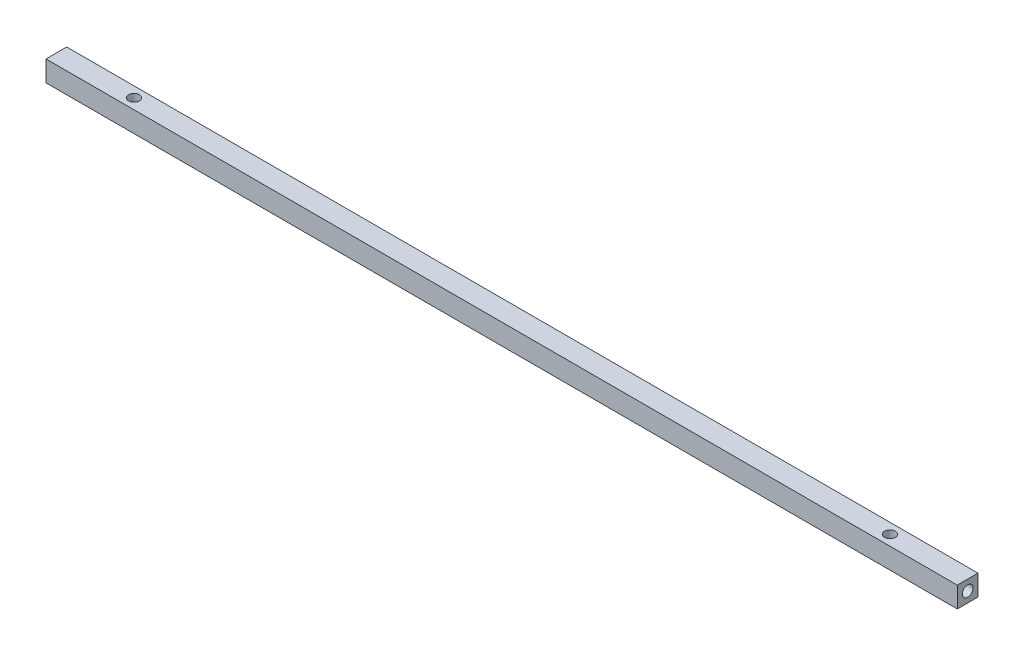
SolidWorks part; units mm, degrees
ref_plane "Front Plane" through (0, 0, 0) normal (0, 0, 1) x (1, 0, 0)
ref_plane "Top Plane" through (0, 0, 0) normal (0, 1, 0) x (1, 0, 0)
ref_plane "Right Plane" through (0, 0, 0) normal (1, 0, 0) x (0, 0, -1)
sketch "Sketch1" plane through (0, 0, 0) normal (1, 0, 0) x (0, 0, -1)
  line L1 (0, 0) -> (6.35, 0)
  line L2 (0, 0) -> (0, 6.35)
  line L3 (0, 6.35) -> (6.35, 6.35)
  line L4 (6.35, 0) -> (6.35, 6.35)
  dimension "D1" = 6.35
extrude "Boss-Extrude1" add sketch "Sketch1" along normal mid plane 279.4
sketch "Sketch2" plane through (0, 0, 0) normal (0, -1, 0) x (1, 0, 0)
  circle A0 centre (-115.8875, -3.175) radius 1.651
  circle A2 centre (-115.8875, -3.175) radius 1.5875 construction
  dimension "D1" = 3.302
extrude "Cut-Extrude1" cut sketch "Sketch2" against normal up to next
sketch "Sketch3" plane through (-139.7, 0, 0) normal (-1, 0, 0) x (0, 0, 1)
  line L0 (0, 0) -> (-6.35, 6.35) construction
  circle A0 centre (-3.175, 3.175) radius 1.651
  dimension "D1" = 3.302
extrude "Cut-Extrude2" cut sketch "Sketch3" against normal blind 19.05
chamfer "Chamfer1" distance 1.5875 angle 45 1 edges at (-115.8875, 0, -4.826)
mirror "Mirror1" about plane through (0, 0, 0) normal (1, 0, 0) of "Cut-Extrude1", "Cut-Extrude2", "Chamfer1"
